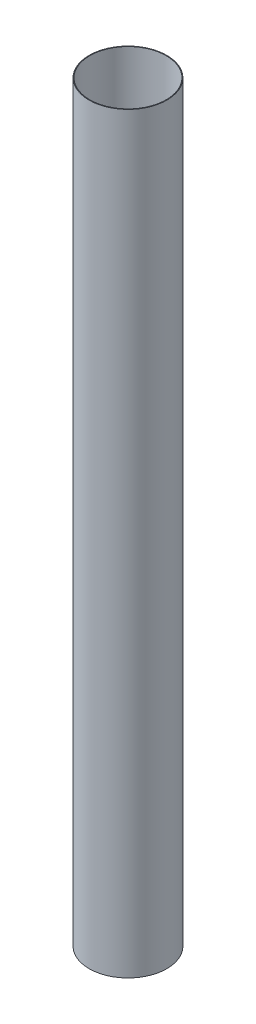
SolidWorks part; units mm, degrees
material "1060 Alloy"
ref_plane "Front Plane" through (0, 0, 0) normal (0, 0, 1) x (1, 0, 0)
ref_plane "Top Plane" through (0, 0, 0) normal (0, 1, 0) x (1, 0, 0)
ref_plane "Right Plane" through (0, 0, 0) normal (1, 0, 0) x (0, 0, -1)
sketch "Sketch1" plane through (0, 0, 0) normal (0, 1, 0) x (1, 0, 0)
  circle A0 centre (0, 0) radius 38.1
  circle A2 centre (0, 0) radius 37.465
  dimension "D1" = 76.2
  dimension "D2" = 74.93
extrude "Boss-Extrude1" add sketch "Sketch1" along normal blind 737.616
